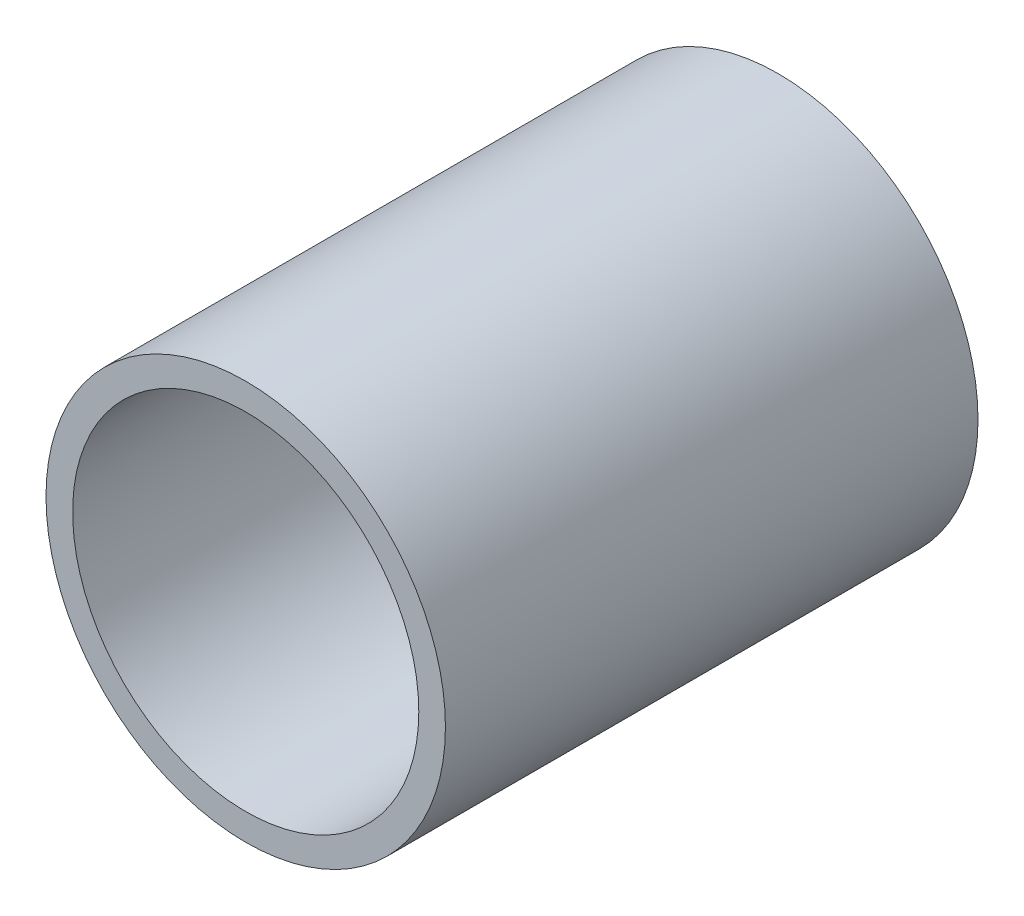
SolidWorks part; units mm, degrees
ref_plane "Front" through (0, 0, 0) normal (0, 0, 1) x (1, 0, 0)
ref_plane "Top" through (0, 0, 0) normal (0, 1, 0) x (1, 0, 0)
ref_plane "Right" through (0, 0, 0) normal (1, 0, 0) x (0, 0, -1)
sketch "Sketch1" plane through (0, 0, 0) normal (0, 0, 1) x (1, 0, 0)
  circle A0 centre (0, 0) radius 7.5
  circle A1 centre (0, 0) radius 6.5
  dimension "D1" = 1
  dimension "D2" = 13
extrude "Boss-Extrude1" add sketch "Sketch1" along normal blind 20
ref_point "Point1"
ref_point "Point2"
ref_axis "Axis1" through (0, 0, 20) along (0, 1, 0)
ref_axis "Axis2" through (0, 0, 0) along (0, 1, 0)
